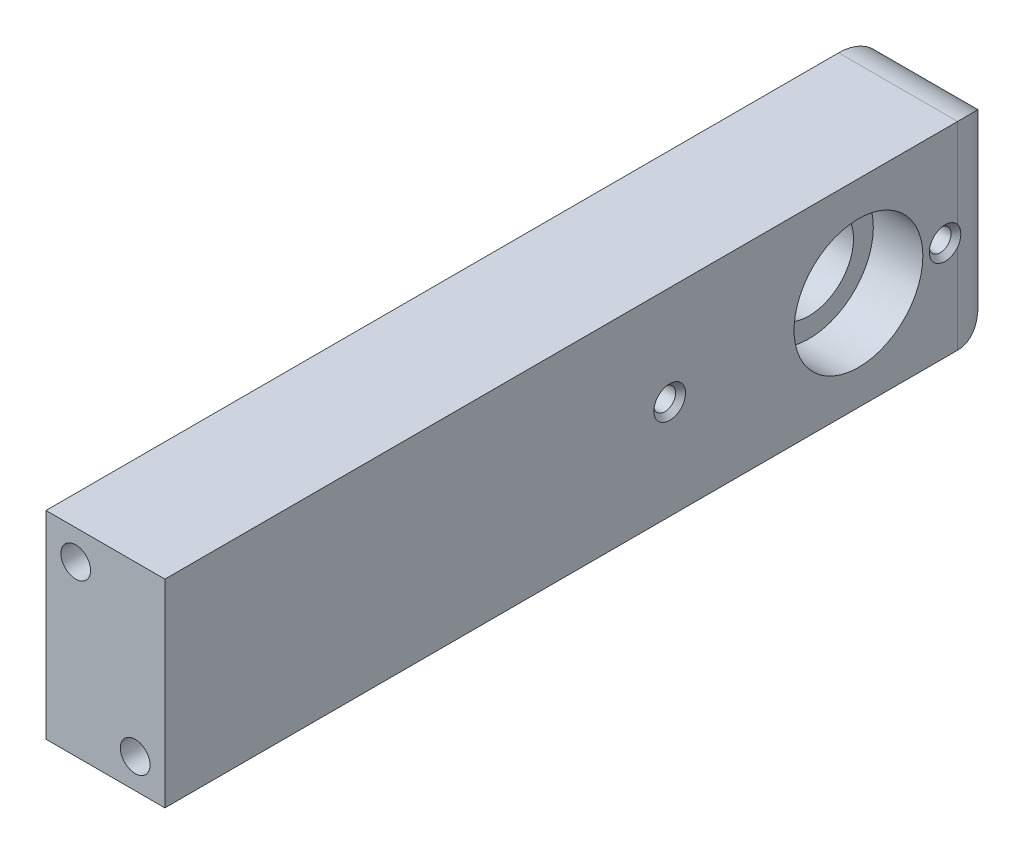
SolidWorks part; units mm, degrees
ref_plane "Płaszczyzna przednia" through (0, 0, 0) normal (0, 0, 1) x (1, 0, 0)
ref_plane "Płaszczyzna górna" through (0, 0, 0) normal (0, 1, 0) x (1, 0, 0)
ref_plane "Płaszczyzna prawa" through (0, 0, 0) normal (1, 0, 0) x (0, 0, -1)
sketch "Szkic1" plane through (0, 0, 0) normal (0, 0, 1) x (1, 0, 0)
  line L1 (-6, -10) -> (6, -10)
  line L2 (-6, -10) -> (-6, 10)
  line L3 (-6, 10) -> (6, 10)
  line L4 (6, -10) -> (6, 10)
  line L5 (-6, -10) -> (6, 10) construction
  line L6 (-6, 10) -> (6, -10) construction
  point P0 (0, 0)
  dimension "D1" = 20
  dimension "D2" = 12
extrude "Dodanie-wyciągnięcie1" add sketch "Szkic1" along normal blind 85
sketch "Szkic2" plane through (0, 0, 85) normal (0, 0, 1) x (1, 0, 0)
  line L0 (6, -10) -> (6, 10) construction
  line L1 (-6, -10) -> (6, -10) construction
  line L2 (-6, 10) -> (-6, -10) construction
  line L3 (6, 10) -> (-6, 10) construction
  circle A0 centre (-3, 7) radius 1.5
  circle A1 centre (3, -7) radius 1.5
  dimension "D1" = 3
  dimension "D2" = 3
  dimension "D3" = 3
  dimension "D4" = 3
  dimension "D5" = 3
  dimension "D6" = 3
extrude "Wytnij-wyciągnięcie1" cut sketch "Szkic2" against normal blind 10
sketch "Szkic4" plane through (6, 0, 0) normal (1, 0, 0) x (0, 0, -1)
  line L0 (-85, 10) -> (0, 10) construction
  line L1 (-85, -10) -> (-85, 10) construction
  circle A0 centre (-15, 0) radius 6.5
  dimension "D1" = 13
  dimension "D2" = 10
  dimension "D3" = 70
extrude "Wytnij-wyciągnięcie2" cut sketch "Szkic4" against normal blind 5
sketch "Szkic5" plane through (-6, 0, 0) normal (-1, 0, 0) x (0, 0, 1)
  line L0 (85, -10) -> (0, -10) construction
  line L1 (85, 10) -> (85, -10) construction
  circle A0 centre (15, 0) radius 4.5
  dimension "D1" = 9
  dimension "D2" = 10
  dimension "D3" = 70
extrude "Wytnij-wyciągnięcie3" cut sketch "Szkic5" against normal through all
sketch "Szkic6" plane through (-6, 0, 0) normal (-1, 0, 0) x (0, 0, 1)
  circle A0 centre (34.05, 0) radius 1.1
extrude "Wytnij-wyciągnięcie4" cut sketch "Szkic6" against normal through all
chamfer "Sfazowanie1" distance 0.5 angle 45 1 edges at (6, 0, 35.15)
sketch "Szkic7" plane through (-6, 0, 0) normal (-1, 0, 0) x (0, 0, 1)
  circle A0 centre (6.25, 0) radius 1.1
extrude "Wytnij-wyciągnięcie5" cut sketch "Szkic7" against normal through all
chamfer "Sfazowanie2" distance 0.5 angle 45 1 edges at (6, 0, 7.35)
fillet "Zaokrąglenie1" radius 5 3 edges at (6, 0, 0) (0, 10, 0) (0, -10, 0)
